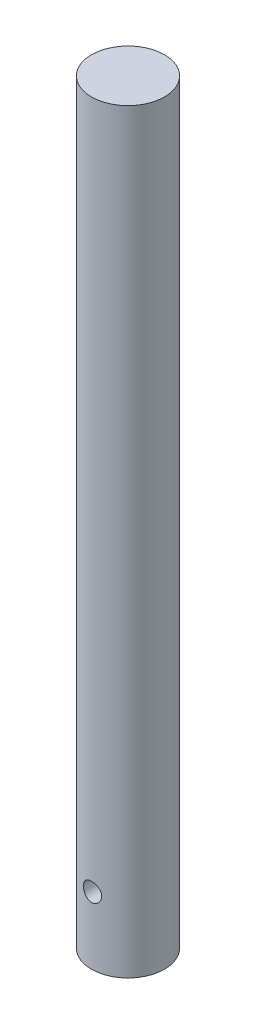
SolidWorks part; units mm, degrees
material "AISI 1020"
ref_plane "Alzado" through (0, 0, 0) normal (0, 0, 1) x (1, 0, 0)
ref_plane "Planta" through (0, 0, 0) normal (0, 1, 0) x (1, 0, 0)
ref_plane "Vista lateral" through (0, 0, 0) normal (1, 0, 0) x (0, 0, -1)
sketch "Croquis4" plane through (0, 0, 0) normal (0, 1, 0) x (1, 0, 0)
  circle A0 centre (0, 0) radius 19.05
  dimension "D1" = 38.1
extrude "Saliente-Extruir2" add sketch "Croquis4" along normal blind 394
sketch "Croquis5" plane through (0, 0, 0) normal (0, 0, 1) x (1, 0, 0)
  circle A0 centre (0, 35) radius 4.765
  dimension "D1" = 9.53
  dimension "35" = 35
extrude "Cortar-Extruir2" cut sketch "Croquis5" against normal through all both and the other way through all
